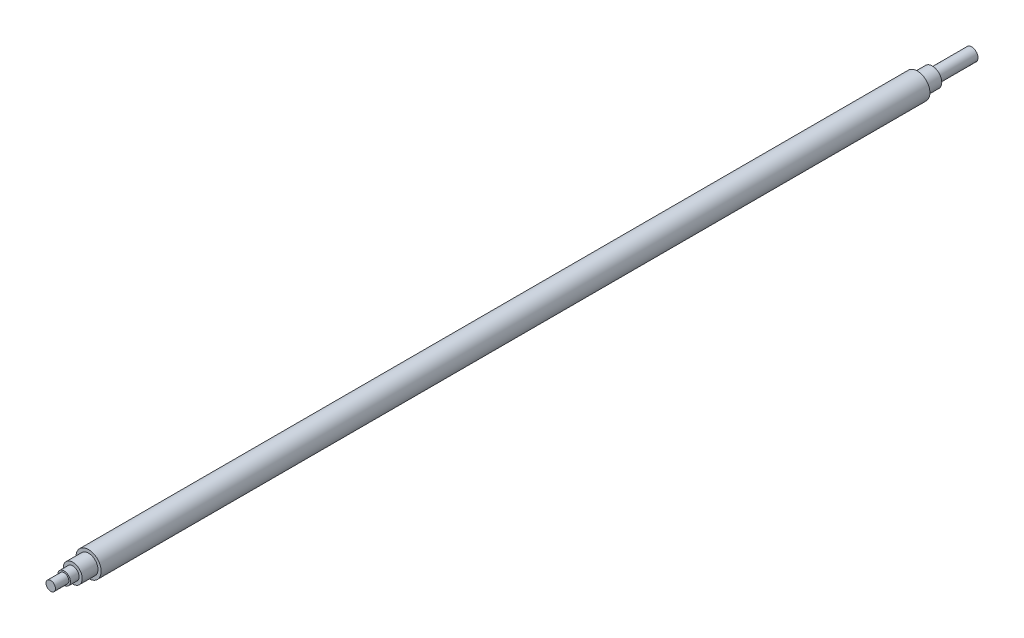
SolidWorks part; units mm, degrees
ref_plane "Piano frontale" through (0, 0, 0) normal (0, 0, 1) x (1, 0, 0)
ref_plane "Piano superiore" through (0, 0, 0) normal (0, 1, 0) x (1, 0, 0)
ref_plane "Piano destro" through (0, 0, 0) normal (1, 0, 0) x (0, 0, -1)
sketch "Schizzo2" plane through (0, 0, 0) normal (1, 0, 0) x (0, 0, -1)
  line L0 (8.5, 0) -> (8.5, 3)
  line L1 (8.5, 3) -> (17, 3)
  line L2 (17, 3) -> (17, 4)
  line L3 (17, 4) -> (22.5, 4)
  line L4 (22.5, 4) -> (22.5, 6)
  line L5 (22.5, 6) -> (32.5, 6)
  line L6 (32.5, 6) -> (32.5, 8)
  line L7 (32.5, 8) -> (558.5, 8)
  line L8 (558.5, 8) -> (558.5, 6)
  line L9 (558.5, 6) -> (568, 6)
  line L10 (568, 6) -> (568, 4)
  line L11 (593, 0) -> (8.5, 0)
  line L14 (593, 0) -> (593, 4)
  line L15 (0, 0) -> (351.0218, 0) construction
  line L18 (568, 4) -> (593, 4)
  point P33 (0, 0)
  dimension "D2" = 6
  dimension "D3" = 8
  dimension "D4" = 12
  dimension "D5" = 16
  dimension "D6" = 12
  dimension "D7" = 8
  dimension "D8" = 8.5
  dimension "D9" = 5.5
  dimension "D10" = 10
  dimension "D11" = 526
  dimension "D12" = 9.5
  dimension "D13" = 25
revolve "Rivoluzione2" add sketch "Schizzo2" angle 360 about L15
